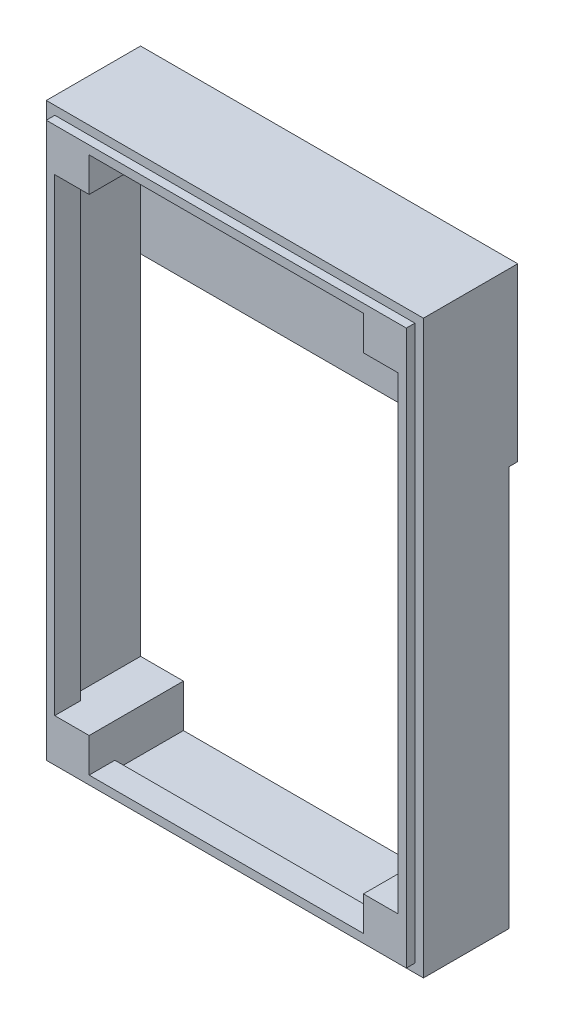
SolidWorks part; units mm, degrees
ref_plane "Спереди" through (0, 0, 0) normal (0, 0, 1) x (1, 0, 0)
ref_plane "Сверху" through (0, 0, 0) normal (0, 1, 0) x (1, 0, 0)
ref_plane "Справа" through (0, 0, 0) normal (1, 0, 0) x (0, 0, -1)
sketch "Эскиз1" plane through (0, 0, 0) normal (0, 0, 1) x (1, 0, 0)
  line L1 (-33, -50) -> (33, -50)
  line L2 (-33, -50) -> (-33, 50)
  line L3 (-33, 50) -> (33, 50)
  line L4 (33, -50) -> (33, 50)
  line L5 (-33, -50) -> (33, 50) construction
  line L6 (-33, 50) -> (33, -50) construction
  line L7 (-31.5, -48.5) -> (31.5, -48.5)
  line L8 (-31.5, -48.5) -> (-31.5, 48.5)
  line L9 (-31.5, 48.5) -> (31.5, 48.5)
  line L10 (31.5, -48.5) -> (31.5, 48.5)
  line L11 (-31.5, -48.5) -> (31.5, 48.5) construction
  line L12 (-31.5, 48.5) -> (31.5, -48.5) construction
  point P0 (0, 0)
  point P6 (0, 0)
  dimension "D1" = 66
  dimension "D2" = 100
  dimension "D3" = 1.5
  dimension "D4" = 1.5
extrude "Бобышка-Вытянуть1" add sketch "Эскиз1" along normal blind 15
sketch "Эскиз2" plane through (0, 0, 0) normal (0, 0, -1) x (-1, 0, 0)
  line L1 (-31.5, 48.5) -> (-24, 48.5)
  line L2 (-31.5, 48.5) -> (-31.5, 41)
  line L3 (-31.5, 41) -> (-24, 41)
  line L4 (-24, 48.5) -> (-24, 41)
  line L5 (31.5, 48.5) -> (24, 48.5)
  line L6 (31.5, 48.5) -> (31.5, 41)
  line L7 (31.5, 41) -> (24, 41)
  line L8 (24, 48.5) -> (24, 41)
  line L9 (-31.5, -48.5) -> (-24, -48.5)
  line L10 (-31.5, -48.5) -> (-31.5, -41)
  line L11 (-31.5, -41) -> (-24, -41)
  line L12 (-24, -48.5) -> (-24, -41)
  line L13 (31.5, -48.5) -> (24, -48.5)
  line L14 (31.5, -48.5) -> (31.5, -41)
  line L15 (31.5, -41) -> (24, -41)
  line L16 (24, -48.5) -> (24, -41)
  dimension "D1" = 7.5
extrude "Бобышка-Вытянуть2" add sketch "Эскиз2" against normal blind 16.5
sketch "Эскиз3" plane through (0, 0, 0) normal (0, 0, -1) x (-1, 0, 0)
  line L0 (33, 50) -> (33, -50) construction
  line L1 (-33, 50) -> (33, 50)
  line L2 (-33, 50) -> (-33, 20)
  line L3 (-33, 20) -> (33, 20)
  line L4 (33, 50) -> (33, 20)
  dimension "D1" = 30
extrude "Бобышка-Вытянуть3" add sketch "Эскиз3" along normal blind 1.5
sketch "Эскиз5" plane through (0, 0, 15) normal (0, 0, 1) x (1, 0, 0)
  line L0 (24, 48.5) -> (-24, 48.5) construction
  line L9 (-30.0247, -47) -> (30.0247, -47)
  line L10 (-30.0247, -47) -> (-30.0247, 47)
  line L11 (-30.0247, 47) -> (30.0247, 47)
  line L12 (30.0247, -47) -> (30.0247, 47)
  line L13 (-30.0247, -47) -> (30.0247, 47) construction
  line L14 (-30.0247, 47) -> (30.0247, -47) construction
  line L15 (-31.5, -48.5) -> (31.5, -48.5)
  line L16 (-31.5, -48.5) -> (-31.5, 48.5)
  line L17 (-31.5, 48.5) -> (31.5, 48.5)
  line L18 (31.5, -48.5) -> (31.5, 48.5)
  line L19 (-31.5, -48.5) -> (31.5, 48.5) construction
  line L20 (-31.5, 48.5) -> (31.5, -48.5) construction
  line L21 (31.5, -41) -> (31.5, 41) construction
  point P0 (0, 0)
  point P6 (0, 0)
  dimension "D1" = 1.5
  dimension "D2" = 1.4753
extrude "Бобышка-Вытянуть9" add sketch "Эскиз5" along normal blind 1.5 and the other way blind 3
